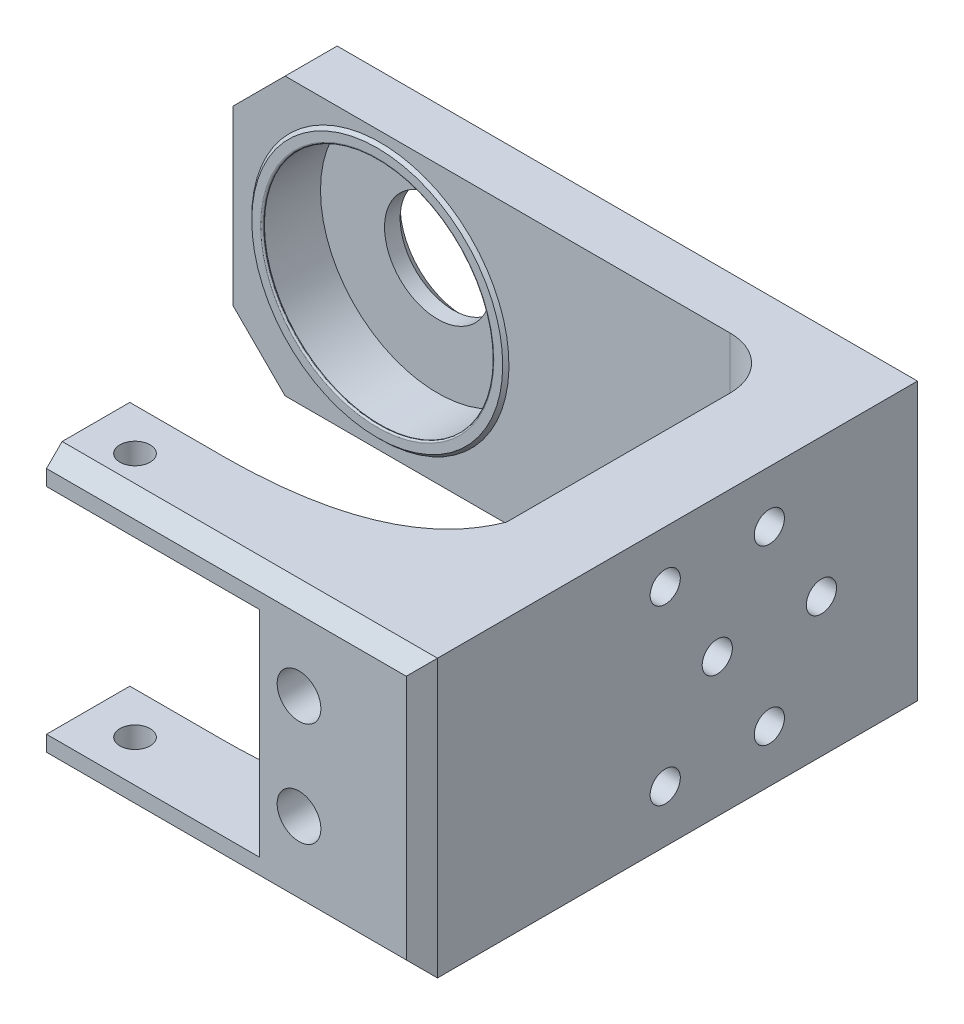
SolidWorks part; units mm, degrees
ref_plane "Alzado" through (0, 0, 0) normal (0, 0, 1) x (1, 0, 0)
ref_plane "Planta" through (0, 0, 0) normal (0, 1, 0) x (1, 0, 0)
ref_plane "Vista lateral" through (0, 0, 0) normal (1, 0, 0) x (0, 0, -1)
sketch "Croquis1" plane through (0, 0, 0) normal (0, 0, 1) x (1, 0, 0)
  line L0 (20.05, -10) -> (-20.05, -10) construction
  line L1 (20.45, -10.3) -> (-20.45, -10.3)
  line L2 (20.45, -10.3) -> (20.45, 10.3)
  line L3 (20.45, 10.3) -> (-20.45, 10.3)
  line L4 (-20.45, -10.3) -> (-20.45, 10.3)
  line L5 (20.45, -10.3) -> (-20.45, 10.3) construction
  line L6 (20.45, 10.3) -> (-20.45, -10.3) construction
  line L7 (-28.05, -13.3) -> (28.05, -13.3)
  line L8 (-28.05, -13.3) -> (-28.05, 13.3)
  line L9 (-28.05, 13.3) -> (28.05, 13.3)
  line L10 (28.05, -13.3) -> (28.05, 13.3)
  line L11 (-28.05, -13.3) -> (28.05, 13.3) construction
  line L12 (-28.05, 13.3) -> (28.05, -13.3) construction
  line L13 (20.25, 9.8) -> (20.25, -9.8) construction
  circle A0 centre (24.25, -5) radius 2.1
  circle A1 centre (24.25, 5) radius 2.1
  circle A2 centre (-24.25, -5) radius 2.1
  circle A3 centre (-24.25, 5) radius 2.1
  point P12 (0, 0)
  point P18 (0, 0)
  dimension "D1" = 4.2
  dimension "D2" = 0.3
  dimension "D3" = 0.2
  dimension "D4" = 3
  dimension "D5" = 7.6
extrude "Saliente-Extruir1" add sketch "Croquis1" along normal blind 8
sketch "Croquis2" plane through (28.05, 0, 0) normal (1, 0, 0) x (0, 0, -1)
  line L0 (-8, -13.3) -> (0, -13.3) construction
  line L1 (-8, 13.3) -> (42.6, 13.3)
  line L2 (-8, 13.3) -> (-8, -13.3)
  line L3 (-8, -13.3) -> (42.6, -13.3)
  line L4 (42.6, 13.3) -> (42.6, -13.3)
  line L5 (39.8, -11.15) -> (39.8, 11.15) construction
  dimension "D1" = 2.8
extrude "Saliente-Extruir2" add sketch "Croquis2" along normal blind 8
sketch "Croquis3" plane through (0, 0, -42.6) normal (0, 0, -1) x (-1, 0, 0)
  line L0 (-28.05, 13.3) -> (28.05, 13.3) construction
  line L1 (-36.05, -13.3) -> (24.686, -13.3)
  line L2 (-36.05, -13.3) -> (-36.05, 13.3)
  line L3 (-36.05, 13.3) -> (24.686, 13.3)
  line L4 (24.686, -13.3) -> (24.686, 13.3)
  line L5 (21.686, 0) -> (21.686, 13.3) construction
  line L6 (28.05, -13.3) -> (-28.05, -13.3) construction
  circle A0 centre (10.536, 0) radius 11.15 construction
  dimension "D1" = 3
extrude "Saliente-Extruir3" add sketch "Croquis3" against normal blind 8
sketch "Croquis4" plane through (0, 0, -34.6) normal (0, 0, 1) x (1, 0, 0)
  circle A0 centre (-10.536, 0) radius 11.25
  circle A1 centre (-10.536, 0) radius 11.15 construction
  dimension "D1" = 0.1
extrude "Cortar-Extruir1" cut sketch "Croquis4" against normal blind 5.5
sketch "Croquis5" plane through (0, 0, -40.1) normal (0, 0, 1) x (1, 0, 0)
  circle A0 centre (-10.536, 0) radius 5.1
  arc A1 (-9.786, 4.4371) -> (-11.286, 4.4371) centre (-10.536, 0) ccw construction
  dimension "D1" = 0.6
extrude "Cortar-Extruir2" cut sketch "Croquis5" against normal through all
sketch "Croquis6" plane through (0, 0, -34.6) normal (0, 0, 1) x (1, 0, 0)
  circle A0 centre (-10.536, 0) radius 11.05
  circle A1 centre (-10.536, 0) radius 11.25 construction
  circle A2 centre (-10.536, 0) radius 12.05
  dimension "D1" = 0.2
  dimension "D2" = 1
extrude "Saliente-Extruir4" add sketch "Croquis6" along normal blind 0.3
chamfer "Chaflán1" distance 0.3 angle 45 1 edges at (1.514, 0, -34.6)
fillet "Redondeo1" radius 0.15 2 edges at (0.514, 0, -34.6) (0.514, 0, -34.3)
chamfer "Chaflán2" distance 5 angle 45 2 edges at (-24.686, 13.3, -38.6) (-24.686, -13.3, -38.6)
sketch "Croquis7" [suppressed] plane through (0, 0, 8) normal (0, 0, 1) x (1, 0, 0)
  line L1 (0, 13.3) -> (36.05, 13.3)
  line L2 (0, 13.3) -> (0, -13.3)
  line L3 (0, -13.3) -> (36.05, -13.3)
  line L4 (36.05, 13.3) -> (36.05, -13.3)
  line L5 (36.05, 13.3) -> (-28.05, 13.3) construction
extrude "Cortar-Extruir3" [suppressed] cut sketch "Croquis7" against normal through all
sketch "Croquis8" [suppressed] plane through (0, 0, 8) normal (0, 0, 1) x (1, 0, 0)
  line L0 (0, 10.3) -> (0, 13.3)
  line L1 (0, 13.3) -> (9, 13.3)
  line L2 (9, 13.3) -> (9, 16.3)
  line L3 (9, 16.3) -> (-3, 16.3)
  line L4 (-3, 16.3) -> (-3, 10.3)
  line L5 (0, 10.3) -> (-20.45, 10.3) construction
  line L6 (-3, 10.3) -> (0, 10.3)
  dimension "D1" = 3
  dimension "D2" = 9
  dimension "D3" = 3
extrude "Saliente-Extruir5" [suppressed] add sketch "Croquis8" against normal up to surface (8 mm away)
chamfer "Chaflán3" [suppressed] distance 3 angle 45
sketch "Croquis9" [suppressed] plane through (0, 0, 0) normal (0, 0, -1) x (-1, 0, 0)
  line L0 (-9, 16.3) -> (-9, 10.3)
  line L1 (-9, 10.3) -> (6, 10.3)
  line L2 (0, 10.3) -> (20.45, 10.3) construction
  line L3 (6, 10.3) -> (6, 13.3)
  line L4 (6, 13.3) -> (3, 16.3)
  line L5 (3, 16.3) -> (-9, 16.3)
extrude "Saliente-Extruir6" [suppressed] add sketch "Croquis9" along normal blind 1.5
ref_plane "Plano1" [suppressed] through (0, 0, 4) normal (0, 0, 1) x (1, 0, 0)
mirror "Simetría1" [suppressed] about plane through (0, 0, 4) normal (0, 0, 1)
chamfer "Chaflán4" [suppressed] distance 1.5 angle 45
sketch "Croquis10" [suppressed] plane through (0, 13.3, 0) normal (0, -1, 0) x (1, 0, 0)
  line L0 (4.5, 8) -> (4.5, 0) construction
  line L1 (9, 8) -> (0, 8) construction
  line L2 (9, 0) -> (0, 0) construction
  line L3 (4.5, 0) -> (4.5, 4) construction
  line L4 (4.5, 4) -> (9, 4) construction
  line L5 (9, 0) -> (9, 8) construction
  circle A0 centre (4.5, 4) radius 1.45
  dimension "D1" = 2.9
extrude "Cortar-Extruir4" [suppressed] cut sketch "Croquis10" against normal through all
fillet "Redondeo2" [suppressed] radius 0.5
mirror "Simetría5" [suppressed] about plane through (0, 0, 0) normal (0, 1, 0)
chamfer "Chaflán5" [suppressed] distance 3 angle 45
chamfer "Chaflán6" [suppressed] distance 1.5 angle 45
chamfer "Chaflán7" [suppressed] distance 3 angle 45
sketch "Croquis11" plane through (0, 0, 8) normal (0, 0, 1) x (1, 0, 0)
  line L1 (0, 13.3) -> (-30.0478, 13.3)
  line L2 (0, 13.3) -> (0, -13.3)
  line L3 (0, -13.3) -> (-30.0478, -13.3)
  line L4 (-30.0478, 13.3) -> (-30.0478, -13.3)
  line L5 (36.05, 13.3) -> (-28.05, 13.3) construction
  line L6 (-28.05, -13.3) -> (36.05, -13.3) construction
extrude "Cortar-Extruir5" cut sketch "Croquis11" against normal up to next
sketch "Croquis12" plane through (0, -13.3, 0) normal (0, -1, 0) x (-1, 0, 0)
  circle A0 centre (-4.5, -4) radius 1.45
  circle A1 centre (-4.5, -4) radius 1.45 construction
extrude "Cortar-Extruir6" cut sketch "Croquis12" against normal through all
chamfer "Chaflán8" distance 3 angle 45 6 edges at (36.05, 0, -42.6) (8.182, -13.3, -42.6) (-22.186, -10.8, -42.6) (-24.686, 0, -42.6) (-22.186, 10.8, -42.6) (8.182, 13.3, -42.6)
chamfer "Chaflán9" distance 1 angle 45 1 edges at (-5.436, 0, -42.6)
chamfer "Chaflán10" distance 1.5 angle 45 3 edges at (18.025, 13.3, 8) (36.05, 0, 8) (18.025, -13.3, 8)
sketch "Croquis13" plane through (0, 13.3, 0) normal (0, 1, 0) x (1, 0, 0)
  line L0 (28.05, 0) -> (0, 0) construction
  line L1 (9, -6.5) -> (9, 1.5) construction
  line L2 (28.05, 34.6) -> (28.05, 0) construction
  line L3 (28.05, 8.1443) -> (28.05, 0)
  line L4 (28.05, 0) -> (9, 0)
  spline S0 degree 2 poles (9, 0) (24.9414, 0.0536) (28.05, 8.1443) knots 0 0 0 0.673634 0.673634 0.673634
extrude "Saliente-Extruir7" add sketch "Croquis13" against normal blind 3
mirror "Simetría7" about plane through (0, 0, 0) normal (0, 1, 0) of "Saliente-Extruir7"
fillet "Redondeo3" radius 5 1 edges at (28.05, 0, -34.6)
sketch "Croquis14" plane through (28.05, 0, 0) normal (-1, 0, 0) x (0, 0, 1)
  line L0 (-25.3722, -8.3) -> (-15.3722, -8.3) construction
  line L1 (-15.3722, -8.3) -> (-15.3722, -13.3) construction
  line L2 (-8.1443, -13.3) -> (-29.6, -13.3) construction
  line L3 (-25.3722, -8.3) -> (-25.3722, -13.3) construction
  line L4 (-25.3722, -8.3) -> (-32.6, -8.3) construction
  line L5 (-32.6, 24.8784) -> (-32.6, -36.1216) construction
  line L6 (-15.3722, -8.3) -> (-8.1443, -8.3) construction
  line L7 (-8.1443, -8.3) -> (-8.1443, -10.3) construction
  circle A0 centre (-15.3722, -8.3) radius 1.45
  circle A1 centre (-25.3722, -8.3) radius 1.45
  dimension "D1" = 2.9
  dimension "D2" = 10
  dimension "D3" = 5
extrude "Cortar-Extruir7" cut sketch "Croquis14" against normal through all
mirror "Simetría8" about plane through (0, 0, 0) normal (0, 1, 0) of "Cortar-Extruir7"
sketch "Croquis15" plane through (28.05, 0, 0) normal (-1, 0, 0) x (0, 0, 1)
  line L0 (-25.3722, -8.3) -> (-15.3722, -8.3) construction
  line L1 (-15.3722, -8.3) -> (-15.3722, 8.3) construction
  line L2 (-15.3722, 8.3) -> (-20.3722, 8.3) construction
  line L3 (-20.3722, 8.3) -> (-20.3722, -8.3) construction
  line L4 (-20.3722, -8.3) -> (-20.3722, 0) construction
  line L5 (-20.3722, 0) -> (-15.3722, 0) construction
  line L6 (-30.3722, 0) -> (-20.3722, 0) construction
  circle A0 centre (-20.3722, 0) radius 1.45
  circle A1 centre (-30.3722, 0) radius 1.45
  circle A2 centre (-15.3722, -8.3) radius 1.45 construction
extrude "Cortar-Extruir8" cut sketch "Croquis15" against normal through all both and the other way through all
